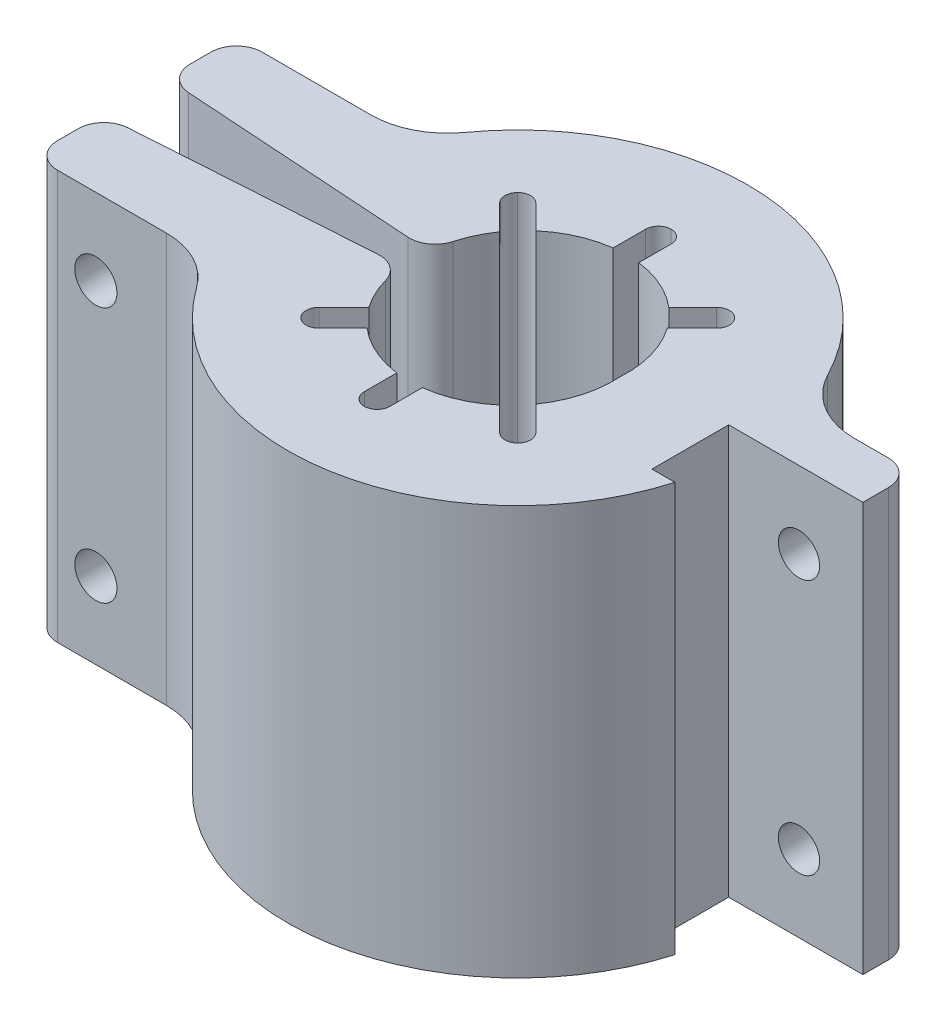
SolidWorks part; units mm, degrees
ref_plane "Front Plane" through (0, 0, 0) normal (0, 0, 1) x (1, 0, 0)
ref_plane "Top Plane" through (0, 0, 0) normal (0, 1, 0) x (1, 0, 0)
ref_plane "Right Plane" through (0, 0, 0) normal (1, 0, 0) x (0, 0, -1)
sketch "Sketch3" plane through (0, 0, 0) normal (1, 0, 0) x (0, 0, -1)
  line L0 (0, 0) -> (0, 73.0645) construction
sketch "Sketch1" plane through (0, 0, 0) normal (0, 1, 0) x (1, 0, 0)
  line L2 (-3.9827, -0.5252) -> (-15, -1.25)
  line L3 (-3.9827, 0.5252) -> (-15, 1.25)
  line L5 (-8.0623, 4) -> (-15, 4)
  line L6 (-8.0623, -4) -> (-15, -4)
  line L7 (-15, 4) -> (-15, 1.25)
  line L8 (-15, -1.25) -> (-15, -4)
  line L10 (8.6458, 2.5) -> (13, 2.5)
  line L11 (8.6458, -2.5) -> (13, -2.5)
  line L12 (13, -2.5) -> (13, 2.5)
  line L13 (-15, 1.25) -> (-15, -1.25) construction
  line L14 (4, 0) -> (-15, 1.25) construction
  line L15 (4, 0) -> (-15, -1.25) construction
  circle A0 centre (0, 0) radius 4 construction
  circle A1 centre (0, 0) radius 9 construction
  arc A5 (8.6458, -2.5) -> (-8.0623, -4) centre (0, 0) cw
  arc A6 (-8.0623, 4) -> (8.6458, 2.5) centre (0, 0) cw
  circle A7 centre (0.0086, 0.2626) radius 4 construction
  circle A8 centre (0.0086, -0.2626) radius 4 construction
  arc A9 (4, 0) -> (-3.9827, 0.5252) centre (0.0086, 0.2626) ccw
  arc A10 (4, 0) -> (-3.9827, -0.5252) centre (0.0086, -0.2626) cw
  point P8 (13, 0)
  point P12 (-15, 0)
  point P24 (4, 0)
  dimension "D1" = 8
  dimension "D2" = 2.5
  dimension "D8" = 9
  dimension "D3" = 5
  dimension "D4" = 13
  dimension "D5" = 8
  dimension "D7" = 15
extrude "Boss-Extrude1" add sketch "Sketch1" along normal blind 16
sketch "Sketch2" plane through (0, 16, 0) normal (0, 1, 0) x (1, 0, 0)
  line L0 (0, 0) -> (0, 6) construction
  line L1 (-0.5, 1) -> (0.5, 1)
  line L2 (-0.5, 1) -> (-0.5, 6)
  line L3 (-0.5, 6) -> (0.5, 6)
  line L4 (0.5, 1) -> (0.5, 6)
  dimension "D1" = 1
  dimension "D2" = 6
  dimension "D3" = 1
extrude "Cut-Extrude1" cut sketch "Sketch2" against normal through all
fillet "Fillet1" radius 0.5 2 edges at (-0.5, 8, -6) (0.5, 8, -6)
pattern_circular "CirPattern1" count 8 over 360 about axis through (0, 0, 0) along (0, 1, 0) skipping 2, 6 of "Cut-Extrude1", "Fillet1" reverse direction yes
sketch "Sketch4" plane through (0, 16, 0) normal (0, 1, 0) x (1, 0, 0)
  line L0 (7.75, -0.5) -> (13, -0.5) construction
  line L1 (7.75, -0.5) -> (7.75, 0.5)
  line L2 (13, -0.5) -> (13, 0.5)
  line L3 (7.75, 0.5) -> (13, 0.5)
  line L4 (7.75, -0.5) -> (13, 0.5) construction
  line L5 (13, -0.5) -> (7.75, 0.5) construction
  line L6 (13, -2.5) -> (13, 2.5) construction
  line L7 (7.75, -0.5) -> (7.75, -2.5)
  line L8 (7.75, -2.5) -> (13, -2.5)
  line L9 (13, -2.5) -> (13, -0.5)
  line L10 (8.6458, -2.5) -> (13, -2.5) construction
  point P0 (13, 0)
  point P1 (10.375, 0)
  point P2 (0, 0)
  dimension "D1" = 1
  dimension "D2" = 5.25
extrude "Cut-Extrude2" cut sketch "Sketch4" against normal through all
sketch "Sketch5" plane through (0, 0, -0.5) normal (0, 0, 1) x (1, 0, 0)
  line L1 (10.5, 3) -> (10.5, 13) construction
  line L2 (-15, 16) -> (-15, 0) construction
  line L3 (13, 0) -> (13, 16) construction
  circle A0 centre (10.5, 13) radius 0.8065
  circle A1 centre (10.5, 3) radius 0.8065
  circle A2 centre (-12.5, 13) radius 0.825
  circle A3 centre (-12.5, 3) radius 0.825
  point P4 (10.5, 8)
  point P5 (0, 0)
  point P7 (13, 8)
  dimension "D1" = 1.6129
  dimension "D5" = 1.65
  dimension "D2" = 2.5
  dimension "D3" = 10
  dimension "D4" = 2.5
extrude "Cut-Extrude3" cut sketch "Sketch5" against normal through all both and the other way through all
fillet "Fillet2" radius 1 7 edges at (13, 8, -2.5) (-15, 8, 4) (-15, 8, -4) (-3.9827, 8, -0.5252) (-3.9827, 8, 0.5252) (-15, 8, 1.25) (-15, 8, -1.25)
fillet "Fillet3" radius 3 3 edges at (8.6458, 8, -2.5) (-8.0623, 8, -4) (-8.0623, 8, 4)
sketch "Sketch7" plane through (0, 0, -2.5) normal (0, 0, -1) x (-1, 0, 0)
  line L1 (-10.5, 15.3671) -> (-12.55, 14.1836)
  line L2 (-12.55, 14.1836) -> (-12.55, 11.8164)
  line L3 (-12.55, 11.8164) -> (-10.5, 10.6329)
  line L4 (-10.5, 10.6329) -> (-8.45, 11.8164)
  line L5 (-8.45, 11.8164) -> (-8.45, 14.1836)
  line L6 (-8.45, 14.1836) -> (-10.5, 15.3671)
  line L7 (-10.5, 5.3671) -> (-12.55, 4.1836)
  line L8 (-12.55, 4.1836) -> (-12.55, 1.8164)
  line L9 (-12.55, 1.8164) -> (-10.5, 0.6329)
  line L10 (-10.5, 0.6329) -> (-8.45, 1.8164)
  line L11 (-8.45, 1.8164) -> (-8.45, 4.1836)
  line L12 (-8.45, 4.1836) -> (-10.5, 5.3671)
  circle A0 centre (-10.5, 13) radius 2.05 construction
  circle A1 centre (-10.5, 3) radius 2.05 construction
  dimension "D1" = 4.1
extrude "Cut-Extrude5" cut sketch "Sketch7" along normal blind 10
